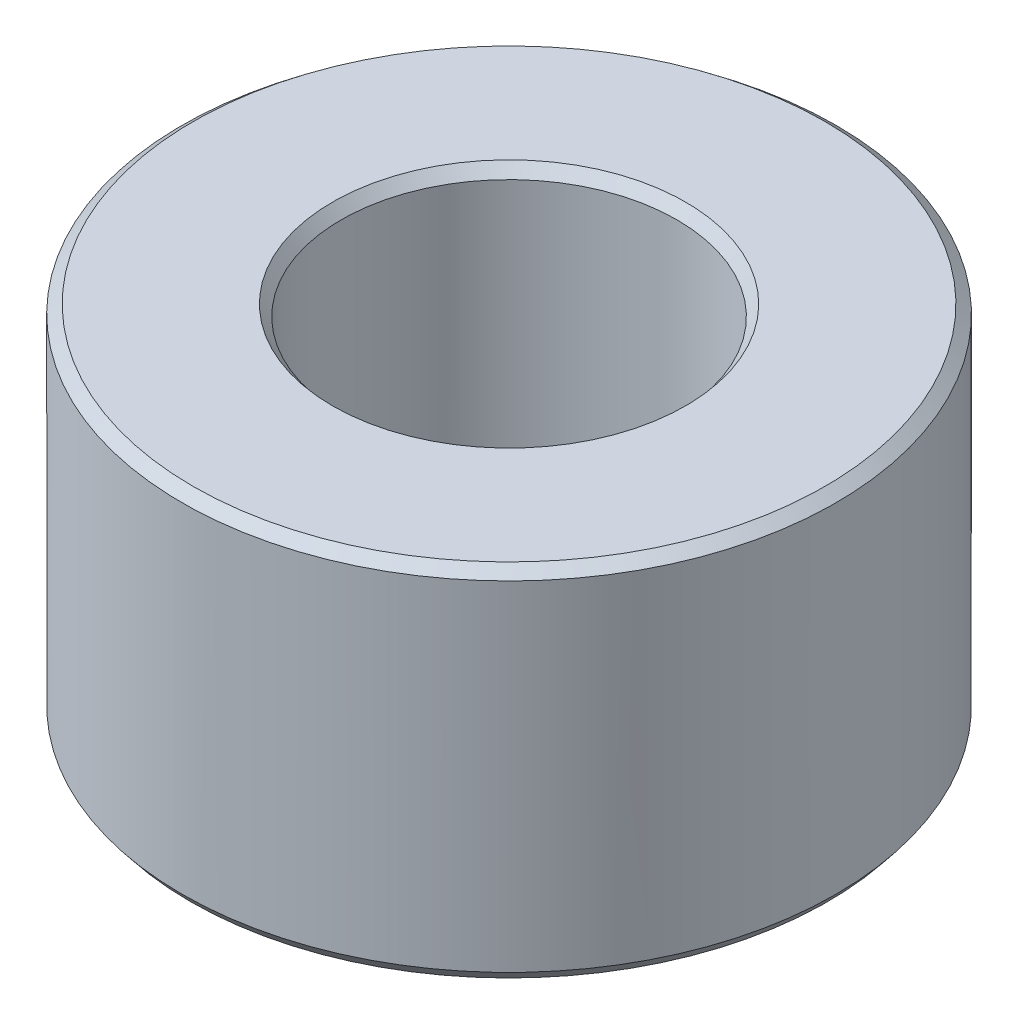
SolidWorks part; units mm, degrees
ref_plane "Front Plane" through (0, 0, 0) normal (0, 0, 1) x (1, 0, 0)
ref_plane "Top Plane" through (0, 0, 0) normal (0, 1, 0) x (1, 0, 0)
ref_plane "Right Plane" through (0, 0, 0) normal (1, 0, 0) x (0, 0, -1)
sketch "Sketch1" plane through (0, 0, 0) normal (0, 1, 0) x (1, 0, 0)
  circle A0 centre (0, 0) radius 42.5
  dimension "SLEEVE_OD" = 85
extrude "Boss-Extrude1" add sketch "Sketch1" along normal blind 46.6252
sketch "Sketch2" plane through (0, 0, 0) normal (0, 1, 0) x (1, 0, 0)
  circle A0 centre (0, 0) radius 21.8168
  dimension "BORE_D" = 43.6336
extrude "Cut-Extrude1" cut sketch "Sketch2" along normal through all
chamfer "Chamfer1" distance 1.1325 angle 51.565 4 edges at (0, 46.6252, 21.8168) (0, 0, 21.8168) (0, 0, 42.5) (0, 46.6252, 42.5) first distance on face at (0, 46.6252, 21.8168) first distance on face at (0, 0, 21.8168) first distance on face at (0, 46.6252, 42.5)
